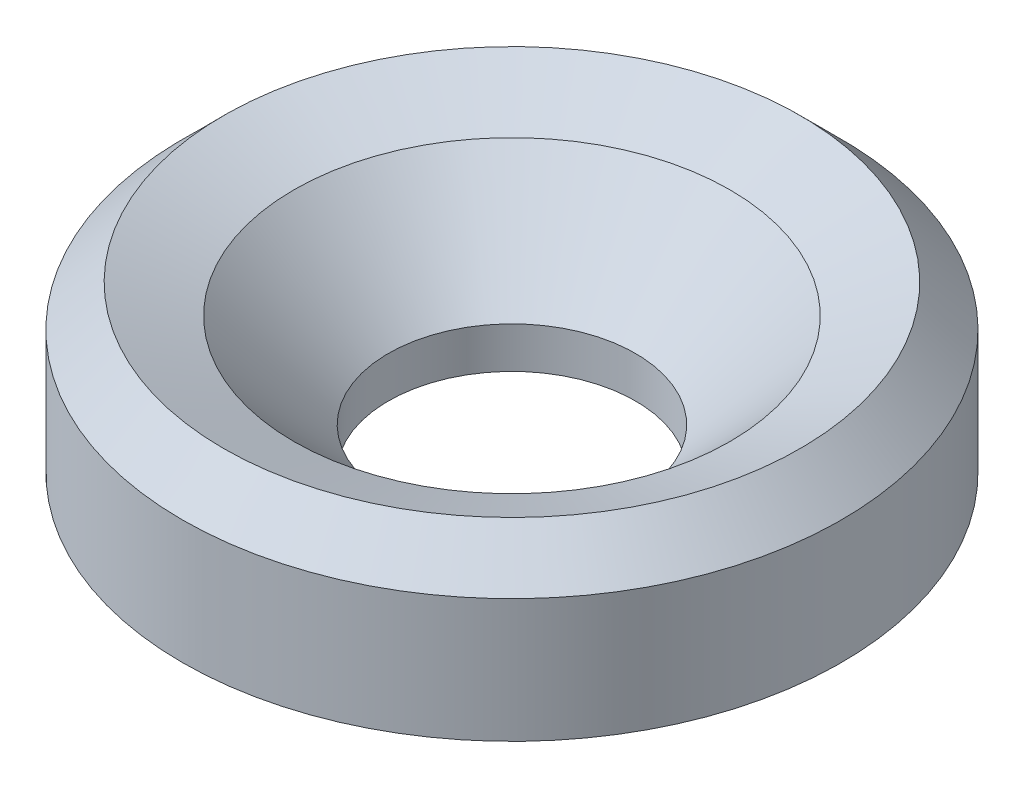
SolidWorks part; units mm, degrees
ref_plane "前视基准面" through (0, 0, 0) normal (0, 0, 1) x (1, 0, 0)
ref_plane "上视基准面" through (0, 0, 0) normal (0, 1, 0) x (1, 0, 0)
ref_plane "右视基准面" through (0, 0, 0) normal (1, 0, 0) x (0, 0, -1)
sketch "草图1" plane through (0, 0, 0) normal (0, 1, 0) x (1, 0, 0)
  circle A0 centre (0, 0) radius 4
  dimension "D1" = 8
extrude "凸台-拉伸1" add sketch "草图1" along normal blind 2
sketch "草图2" plane through (0, 2, 0) normal (0, 1, 0) x (1, 0, 0)
  circle A0 centre (0, 0) radius 1.5
  dimension "D1" = 3
extrude "切除-拉伸1" cut sketch "草图2" against normal through all
chamfer "倒角1" distance 1.5 1 edges at (0, 2, 1.5)
chamfer "倒角2" distance 0.5 2 edges at (0, 2, 4) (0, 2, 3)
